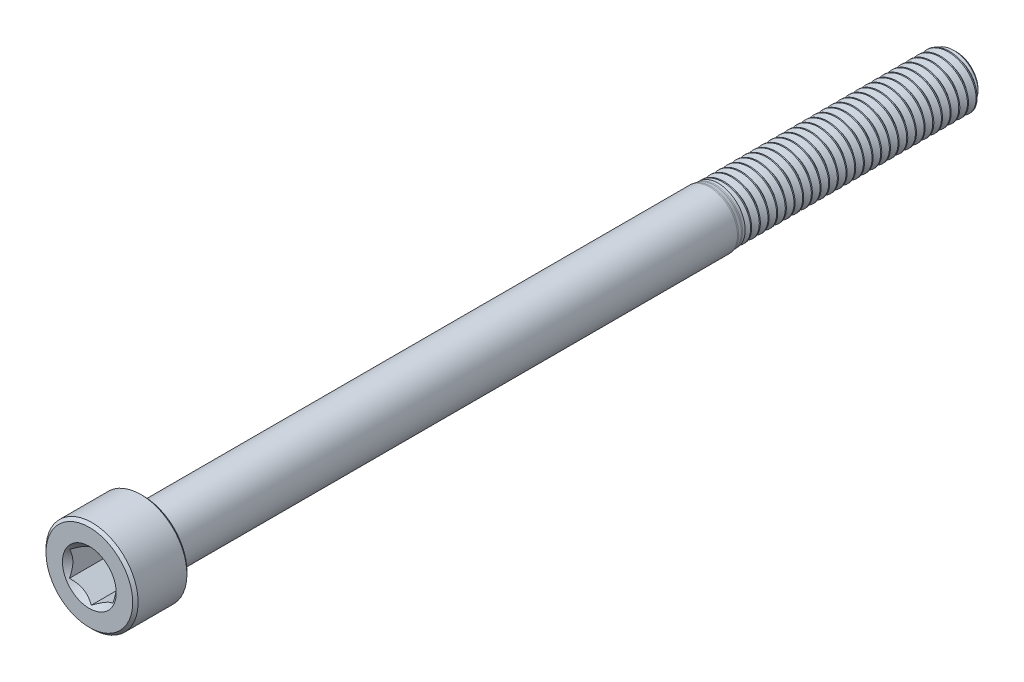
SolidWorks part; units mm, degrees
ref_plane "Front Plane" through (0, 0, 0) normal (0, 0, 1) x (1, 0, 0)
ref_plane "Top Plane" through (0, 0, 0) normal (0, 1, 0) x (1, 0, 0)
ref_plane "Right Plane" through (0, 0, 0) normal (1, 0, 0) x (0, 0, -1)
sketch "Sketch1" plane through (0, 0, 0) normal (1, 0, 0) x (0, 0, -1)
  line L0 (-40, 0) -> (40, 0) construction
  line L1 (40, 0) -> (40, 1.9804) construction
  line L2 (40, 1.9804) -> (39.4804, 2.5) construction
  line L3 (39.4804, 2.5) -> (39.4, 2.5) construction
  line L4 (39.4, 2.5) -> (-35, 2.5) construction
  line L5 (-35, 2.5) -> (-35, 4.25) construction
  line L6 (-35, 4.25) -> (-40, 4.25) construction
  line L7 (-40, 4.25) -> (-40, 0) construction
  line L8 (40, 1.9804) -> (40, 2.5) construction
  line L9 (39.95, 2.5866) -> (40.35, 1.8938) construction
  line L10 (40.35, 1.8938) -> (40.75, 2.5866) construction
  line L11 (40.75, 2.5866) -> (39.95, 2.5866) construction
  line L12 (40.35, 2.5866) -> (40.35, 2.5) construction
  line L13 (40.35, 1.8938) -> (40.35, 1.9804) construction
  line L14 (40.3, 1.9804) -> (40.4, 1.9804) construction
  line L15 (40, 2.5) -> (40.7, 2.5) construction
  line L16 (39.975, 2.5433) -> (40.725, 2.5433) construction
  line L17 (40, 0) -> (40, -2.5) construction
  line L18 (-35.25, 4.25) -> (-35, 4) construction
  line L19 (-39.75, 4.25) -> (-40, 4) construction
  line L20 (-35, 2.5) -> (-35, 0) construction
  line L21 (-35, 1.25) -> (-10, 1.25) construction
  line L22 (-10, 1.25) -> (15, 1.25) construction
  line L23 (15, 1.25) -> (40, 1.25) construction
  line L24 (-10, 1.25) -> (-10, 2.5) construction
  line L25 (-10, 2.5) -> (-10, 4.25) construction
  line L26 (15, 1.25) -> (15, 4.25) construction
  point P0 (-40, 2)
  point P3 (38, 2.5)
  point P4 (0, 0)
  point P18 (15, 2.5)
  point P22 (40.35, 1.9804)
  point P24 (39.4, 2.5)
  point P25 (40.35, 2.5)
  point P28 (40.35, 2.5433)
  point P29 (38, -2.5)
  point P30 (-10, 2.5)
  point P31 (-37.5, 4.25)
  point P37 (-35.875, 4.25)
  point P38 (-39.625, 4.25)
  point P45 (-10, 1.25)
  point P46 (15, 1.25)
  point P49 (18, 2.5)
  dimension "D1" = 45
  dimension "D2" = 0.1
  dimension "D7" = 0.25
  dimension "D8" = 0.25
  dimension "D9" = 0.25
  dimension "D10" = 0.125
  dimension "D11" = 0.625
  dimension "Drive Size" = 4
  dimension "Head Diameter" = 8.5
  dimension "Head Height" = 5
  dimension "Thread Pitch" = 0.8
  dimension "Thread Dia" = 5
  dimension "Length" = 75
  dimension "D12" = 0.6
  dimension "D4" = 2
  dimension "Minimum Thread Length" = 22
  dimension "D3" = 53
sketch "Sketch2" plane through (0, 0, 0) normal (1, 0, 0) x (0, 0, -1)
  line L0 (-40, 0) -> (-40, 4)
  line L1 (-39.75, 4.25) -> (-35.25, 4.25)
  line L2 (-35, 4) -> (-35, 2.8366)
  line L4 (39.4804, 2.5) -> (40, 1.9804)
  line L5 (40, 1.9804) -> (40, 0)
  line L6 (-35, 4.25) -> (-40, 4.25) construction
  line L7 (40, 0) -> (-40, 0)
  line L8 (-39.75, 4.25) -> (-40, 4) construction
  line L10 (-39.75, 4.25) -> (-40, 4)
  line L14 (-35.25, 4.25) -> (-35, 4) construction
  line L16 (-35.25, 4.25) -> (-35, 4)
  line L17 (-35, 2.5) -> (-35, 4.25) construction
  line L18 (-34.75, 2.5866) -> (17.2031, 2.5866)
  line L19 (17.7616, 2.5) -> (39.4804, 2.5)
  line L20 (39.4, 2.5) -> (-35, 2.5) construction
  line L21 (17.325, 2.5746) -> (17.6396, 2.512)
  line L22 (40.75, 2.5866) -> (39.95, 2.5866) construction
  arc A1 (-35, 2.8366) -> (-34.75, 2.5866) centre (-34.75, 2.8366) ccw
  arc A2 (17.2031, 2.5866) -> (17.325, 2.5746) centre (17.2031, 1.9616) cw
  arc A3 (17.6396, 2.512) -> (17.7616, 2.5) centre (17.7616, 3.125) ccw
  point P39 (17.7, 2.5)
  dimension "D3" = 0.25
  dimension "D6" = 0.625
  dimension "D4" = 11.25
  dimension "D5" = 0.3
revolve "Revolve1" add sketch "Sketch2" angle 360 about L7
sketch "Sketch3" plane through (0, 0, 40) normal (0, 0, 1) x (1, 0, 0)
  line L1 (2, -1.1547) -> (2, 1.1547)
  line L2 (2, 1.1547) -> (0, 2.3094)
  line L3 (0, 2.3094) -> (-2, 1.1547)
  line L4 (-2, 1.1547) -> (-2, -1.1547)
  line L5 (-2, -1.1547) -> (0, -2.3094)
  line L6 (0, -2.3094) -> (2, -1.1547)
  circle A0 centre (0, 0) radius 2 construction
  circle A1 centre (0, 0) radius 4.25 construction
  circle A2 centre (0, 0) radius 4.25 construction
  circle A3 centre (0, 0) radius 2.3094 construction
  dimension "D1" = 4.6188
extrude "Cut-Extrude1" cut sketch "Sketch3" against normal offset from surface (4 mm away) 1 up to face at (0, 4, 35)
sketch "Sketch4" plane through (0, 0, 40) normal (0, 0, 1) x (1, 0, 0)
  circle A0 centre (0, 0) radius 2.4826
  dimension "D1" = 4.9652
extrude "Cut-Extrude2" cut sketch "Sketch4" against normal up to vertex (2.5 mm away) draft 45 up to point (0, 4.25, 37.5)
sketch "Sketch11" plane through (0, 0, 0) normal (1, 0, 0) x (0, 0, -1)
  line L0 (-40, 0) -> (40, 0) construction
  line L1 (-40, 0) -> (40, 0) construction
  line L2 (-30.3625, 0) -> (-30.3625, 2.5) construction
  line L3 (39.4, 2.5) -> (-35, 2.5) construction
  line L4 (12.5656, 0) -> (12.5656, 2.5) construction
  point P2 (-30.3625, 0)
  point P3 (12.5656, 0)
  dimension "D1" = 4.6375
  dimension "D2" = 4.6375
sketch "Sketch6" plane through (0, 0, -40) normal (0, 0, -1) x (-1, 0, 0)
  circle A0 centre (0, 0) radius 2.5
curve "Helix/Spiral1" pitch 0.8 height 22.8 radius 2.5 centre (0, 0, -40) axis (0, 0, 1) start towards (0, 1, 0)
sketch "Sketch10" plane through (0, 0, 0) normal (1, 0, 0) x (0, 0, -1)
  line L0 (18, -2.5) -> (18, 2.5)
  line L2 (-40, 0) -> (40, 0) construction
  point P3 (18, 0)
split "Split1" trim tools "Sketch10" bodies to split 106 resulting bodies 114 115
sketch "Sketch7" plane through (0, 0, 0) normal (1, 0, 0) x (0, 0, -1)
  line L0 (39.975, 2.5433) -> (40.725, 2.5433)
  line L1 (40.725, 2.5433) -> (40.4, 1.9804)
  line L2 (40.4, 1.9804) -> (40.3, 1.9804)
  line L3 (40.3, 1.9804) -> (39.975, 2.5433)
sweep "Cut-Sweep1" cut profiles "Sketch7" path "Helix/Spiral1" align with end faces yes
sketch "Sketch8" plane through (0, 0, 0) normal (1, 0, 0) x (0, 0, -1)
  line L0 (-35, 0) -> (-35, 2.5)
  line L2 (-35, 2.5) -> (18, 2.5)
  line L4 (18, 2.5) -> (19.4434, 0)
  line L5 (19.4434, 0) -> (-35, 0)
  line L6 (39.4, 2.5) -> (-35, 2.5) construction
  line L7 (-40, 0) -> (40, 0) construction
  dimension "D1" = 60
  dimension "D2" = 22
revolve "Revolve2" add sketch "Sketch8" angle 360 about L5
equation "\"D2@Sketch1\" = \"Thread Pitch@Sketch1\" / 8"
equation "\"D4@Helix/Spiral1\" = \"Thread Pitch@Sketch1\""
equation "\"D7@Sketch1\" = \"Head Height@Sketch1\" * .05"
equation "\"D8@Sketch1\"=\"D7@Sketch1\""
equation "\"D9@Sketch1\"=\"D7@Sketch1\""
equation "\"D10@Sketch1\"=\"D7@Sketch1\"/2"
equation "\"D11@Sketch1\"=\"D10@Sketch1\"*5"
equation "\"D4@Sketch1\"=\"Thread Pitch@Sketch1\"*2.5"
equation "\"D12@Sketch1\"=\"Thread Pitch@Sketch1\"*.75"
equation "\"D3@Helix/Spiral1\"=\"Minimum Thread Length@Sketch1\"+\"Thread Pitch@Sketch1\""
equation "\"D2@Sketch8\"=\"Minimum Thread Length@Sketch1\""
equation "\"D3@Sketch2\"=\"Thread Dia@Sketch1\"*0.05"
equation "\"D5@Sketch2\"=\"D12@Sketch1\"*0.5"
equation "\"D6@Sketch2\"=\"Thread Dia@Sketch1\"*0.125"
equation "\"D1@Sketch11\"=\"D3@Sketch1\"*0.0875"
equation "\"D2@Sketch11\"=\"D1@Sketch11\""
equation "\"D1@Sketch4\"=\"D1@Sketch3\"*1.075"
